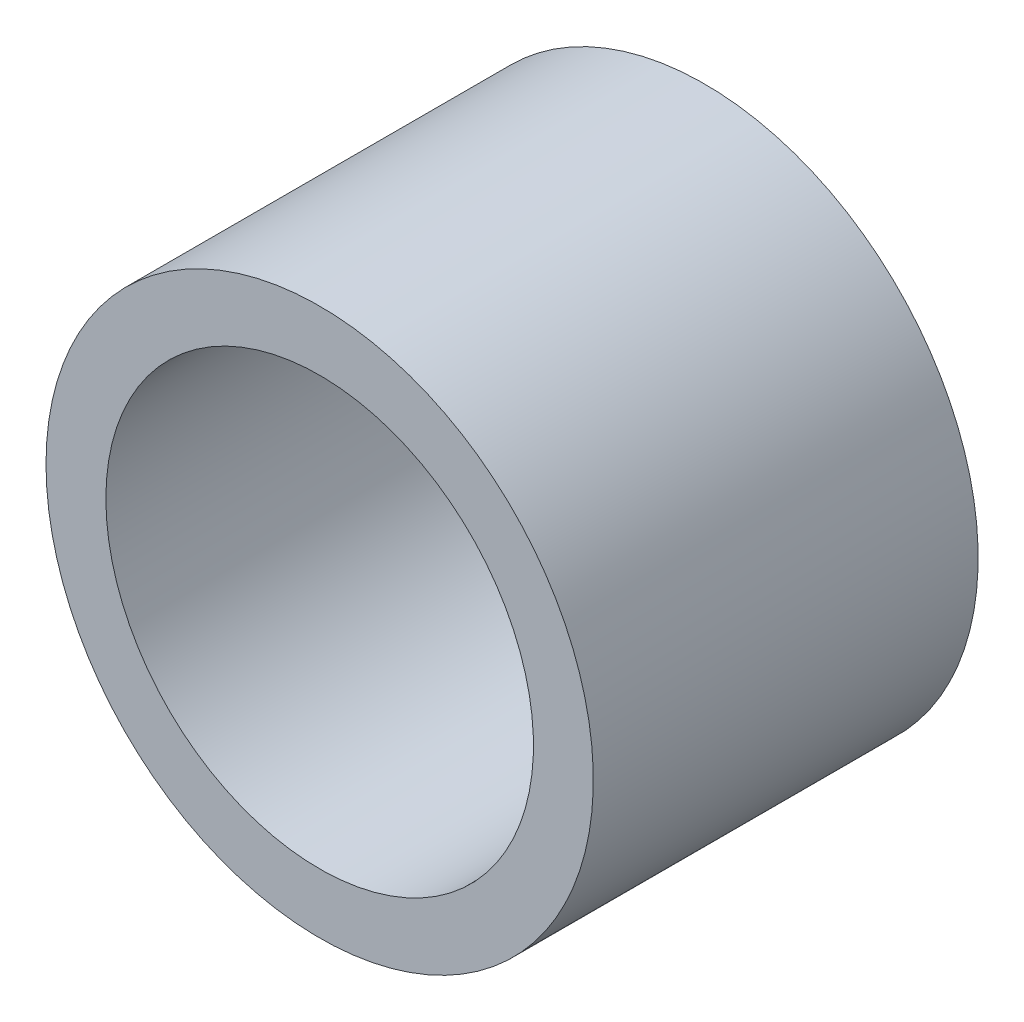
SolidWorks part; units mm, degrees
ref_plane "Спереди" through (0, 0, 0) normal (0, 0, 1) x (1, 0, 0)
ref_plane "Сверху" through (0, 0, 0) normal (0, 1, 0) x (1, 0, 0)
ref_plane "Справа" through (0, 0, 0) normal (1, 0, 0) x (0, 0, -1)
sketch "Эскиз1" plane through (0, 0, 0) normal (0, 0, 1) x (1, 0, 0)
  circle A0 centre (0, 0) radius 16
extrude "Вытянуть1" add sketch "Эскиз1" along normal blind 22.5
sketch "Эскиз2" plane through (0, 0, 0) normal (0, 0, -1) x (-1, 0, 0)
  circle A0 centre (0, 0) radius 15
extrude "Вытянуть3" cut sketch "Эскиз2" against normal blind 4
sketch "Эскиз3" plane through (0, 0, 4) normal (0, 0, -1) x (-1, 0, 0)
  circle A0 centre (0, 0) radius 12.5
extrude "Вытянуть4" cut sketch "Эскиз3" against normal through all
